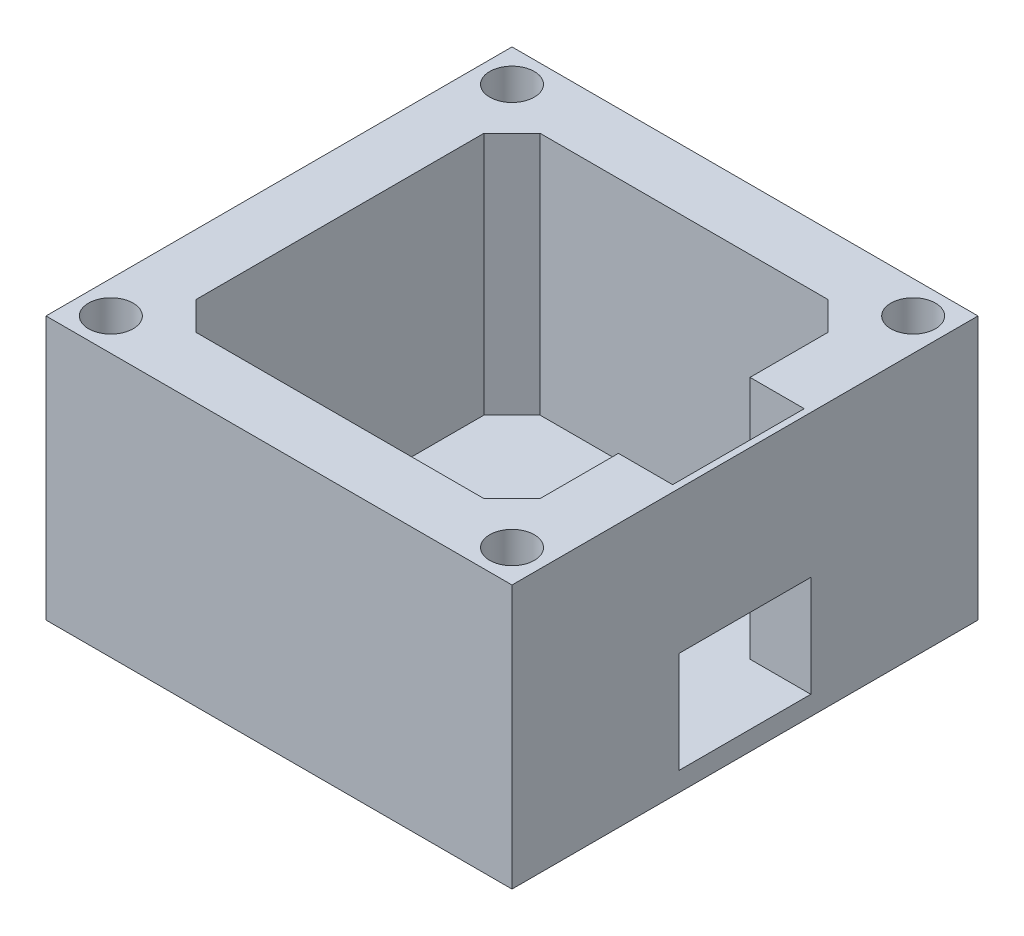
SolidWorks part; units mm, degrees
ref_plane "Front Plane" through (0, 0, 0) normal (0, 0, 1) x (1, 0, 0)
ref_plane "Top Plane" through (0, 0, 0) normal (0, 1, 0) x (1, 0, 0)
ref_plane "Right Plane" through (0, 0, 0) normal (1, 0, 0) x (0, 0, -1)
sketch "Sketch1" plane through (0, 0, 0) normal (0, 1, 0) x (1, 0, 0)
  line L1 (0, 0) -> (58.42, 0)
  line L2 (0, 0) -> (0, 58.42)
  line L3 (0, 58.42) -> (58.42, 58.42)
  line L4 (58.42, 0) -> (58.42, 58.42)
  dimension "D1" = 58.42
  dimension "D2" = 58.42
extrude "Boss-Extrude1" add sketch "Sketch1" along normal blind 33.02
sketch "Sketch2" plane through (0, 33.02, 0) normal (0, 1, 0) x (1, 0, 0)
  line L0 (11.1555, 50.8) -> (47.2645, 50.8)
  line L1 (47.2645, 50.8) -> (50.8, 47.2645)
  line L2 (50.8, 47.2645) -> (50.8, 37.46)
  line L3 (50.8, 11.1555) -> (47.2645, 7.62)
  line L4 (47.2645, 7.62) -> (11.1555, 7.62)
  line L5 (11.1555, 7.62) -> (7.62, 11.1555)
  line L6 (7.62, 11.1555) -> (7.62, 47.2645)
  line L7 (7.62, 47.2645) -> (11.1555, 50.8)
  line L8 (50.8, 20.96) -> (50.8, 11.1555)
  line L9 (50.8, 37.46) -> (57.6, 37.46)
  line L10 (50.8, 20.96) -> (57.6, 20.96)
  line L11 (57.6, 37.46) -> (57.6, 20.96)
  line L12 (58.42, 58.42) -> (0, 58.42) construction
  line L13 (0, 58.42) -> (0, 0) construction
  point P9 (7.62, 29.21)
  point P14 (57.6, 29.21)
  point P17 (29.21, 58.42)
  point P18 (29.21, 50.8)
  point P21 (0, 29.21)
  dimension "D1" = 5
  dimension "D2" = 43.18
  dimension "D3" = 135
  dimension "D4" = 135
  dimension "D5" = 135
  dimension "D6" = 43.18
  dimension "D7" = 16.5
  dimension "D8" = 6.8
extrude "Cut-Extrude1" cut sketch "Sketch2" against normal blind 30.6
sketch "Sketch3" plane through (58.42, 0, 0) normal (1, 0, 0) x (0, 0, -1)
  line L0 (20.96, 15.12) -> (37.46, 15.12)
  line L1 (20.96, 15.12) -> (20.96, 2.42)
  line L2 (20.96, 2.42) -> (37.46, 2.42)
  line L3 (37.46, 15.12) -> (37.46, 2.42)
  line L4 (0, 33.02) -> (58.42, 33.02) construction
  point P4 (29.21, 33.02)
  point P7 (29.21, 15.12)
  dimension "D1" = 16.5
  dimension "D2" = 12.7
  dimension "D3" = 30.6
extrude "Cut-Extrude2" cut sketch "Sketch3" against normal blind 30.6
sketch "Sketch4" plane through (0, 33.02, 0) normal (0, 1, 0) x (1, 0, 0)
  line L0 (58.42, 58.42) -> (0, 58.42) construction
  line L1 (0, 58.42) -> (0, 0) construction
  line L2 (29.21, 58.42) -> (29.21, 0) construction
  line L3 (0, 0) -> (58.42, 0) construction
  line L4 (0, 29.21) -> (58.42, 29.21) construction
  line L5 (58.42, 0) -> (58.42, 58.42) construction
  circle A0 centre (4.064, 54.356) radius 2.794
  circle A1 centre (54.356, 54.356) radius 2.794
  circle A2 centre (54.356, 4.064) radius 2.794
  circle A3 centre (4.064, 4.064) radius 2.794
  dimension "D1" = 5.588
  dimension "D2" = 4.064
  dimension "D3" = 4.064
extrude "Cut-Extrude3" cut sketch "Sketch4" against normal through all
